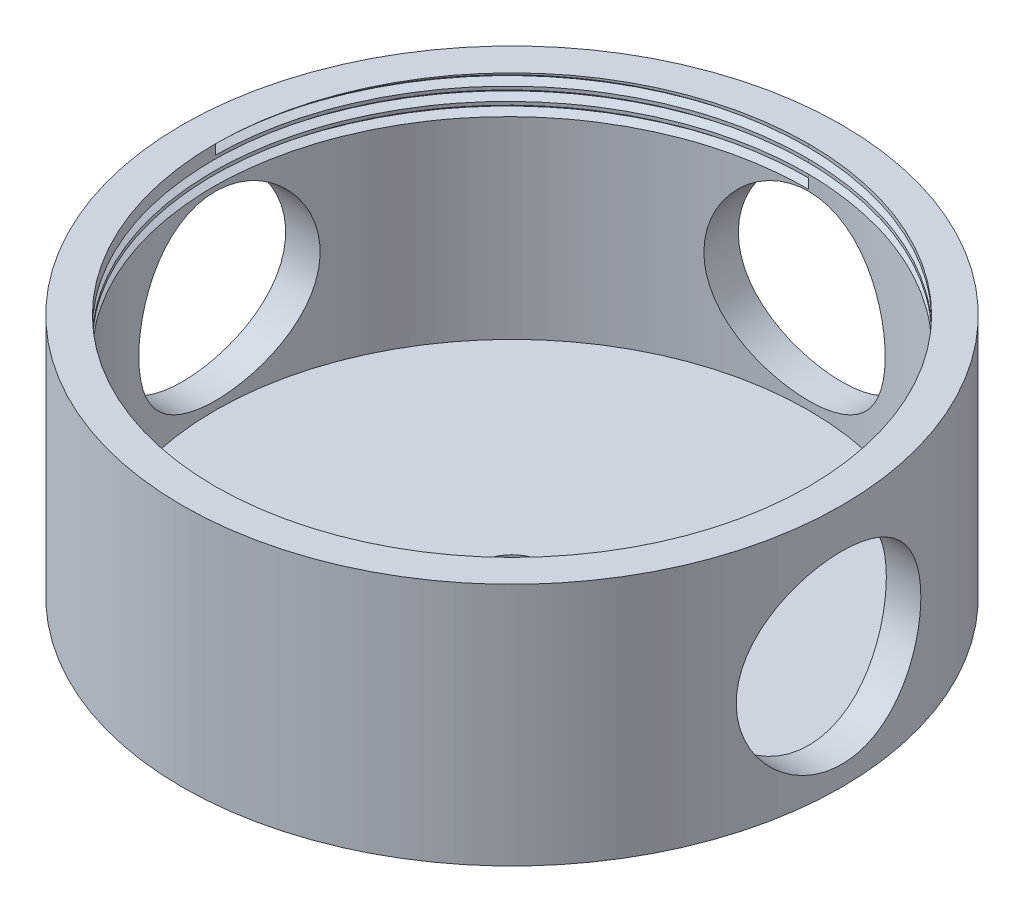
SolidWorks part; units mm, degrees
ref_plane "Front Plane" through (0, 0, 0) normal (0, 0, 1) x (1, 0, 0)
ref_plane "Top Plane" through (0, 0, 0) normal (0, 1, 0) x (1, 0, 0)
ref_plane "Right Plane" through (0, 0, 0) normal (1, 0, 0) x (0, 0, -1)
sketch "Sketch1" plane through (0, 0, 0) normal (0, 1, 0) x (1, 0, 0)
  circle A0 centre (0, 0) radius 50
  dimension "D1" = 100
extrude "Boss-Extrude1" add sketch "Sketch1" along normal blind 2 contours A0
sketch "Sketch2" plane through (0, 2, 0) normal (0, 1, 0) x (1, 0, 0)
  circle A0 centre (0, 0) radius 50
  circle A1 centre (0, 0) radius 45
  dimension "D1" = 100
  dimension "D2" = 5
extrude "Boss-Extrude2" add sketch "Sketch2" along normal blind 35
ref_plane "Plane3" through (0, 0, 40) normal (0, 0, 1) x (1, 0, 0)
sketch "Sketch5" plane through (0, 0, 40) normal (0, 0, 1) x (1, 0, 0)
  line L0 (-50, 0) -> (50, 0) construction
  line L1 (-26.6422, 0) -> (27.3578, 0)
  line L2 (-26.6422, 0) -> (-26.6422, -34)
  line L3 (-26.6422, -34) -> (27.3578, -34)
  line L4 (27.3578, 0) -> (27.3578, -34)
  line L5 (-50, 0) -> (50, 0) construction
  line L6 (-24.6422, -2) -> (25.3578, -2)
  line L7 (-24.6422, -2) -> (-24.6422, -32)
  line L8 (-24.6422, -32) -> (25.3578, -32)
  line L9 (25.3578, -2) -> (25.3578, -32)
  dimension "D1" = 2
  dimension "D2" = 2
  dimension "D3" = 2
  dimension "D4" = 2
  dimension "D5" = 50
  dimension "D6" = 2
  dimension "D7" = 30
thread "Thread1" pitch 2 method cut profile "Thread Profile1" start angle 0, offset 0, length 4.5, pitch 2, diameter 90
ref_plane "Plane4" through (-45, 37, 0) normal (0, 0, 1) x (-1, 0, 0)
sketch "Thread Profile1" plane through (-45, 37, 0) normal (0, 0, 1) x (-1, 0, 0)
  line L0 (0, 0) -> (0, 2) construction
  line L1 (0, 0) -> (1.0825, 0.625)
  line L2 (1.0825, 0.625) -> (1.0825, 0.875)
  line L3 (1.0825, 0.875) -> (0, 1.5)
  line L4 (1.0825, 0.75) -> (0, 0.75) construction
  line L11 (0, 0) -> (0, 1.5)
  point P2 (0, 0)
  dimension "Pitch" = 2
  dimension "Profile_Angle" = 60
  dimension "Profile_Land" = 0.25
  dimension "Profile_Height" = 1.0825
ref_plane "Plane6" through (0, 0, -50) normal (0, 0, -1) x (-1, 0, 0)
sketch "Sketch10" plane through (0, 0, -50) normal (0, 0, -1) x (-1, 0, 0)
  line L0 (0, 17) -> (-42.3594, 17) construction
  line L1 (0, 37) -> (0, 0) construction
  line L2 (50, 37) -> (-50, 37) construction
  line L3 (-42.3594, 17) -> (37.1989, 17) construction
  circle A1 centre (0, 17) radius 13.75
  dimension "D2" = 27.5
  dimension "D5" = 37
  dimension "D6" = 20
extrude "Cut-Extrude2" cut sketch "Sketch10" against normal up to next
ref_plane "Plane8" through (-50, 0, 0) normal (-1, 0, 0) x (0, 0, 1)
sketch "Sketch12" plane through (-50, 0, 0) normal (-1, 0, 0) x (0, 0, 1)
  line L1 (50, 37) -> (-50, 37) construction
  circle A0 centre (0, 17) radius 13.75
  dimension "D1" = 27.5
  dimension "D2" = 20
extrude "Cut-Extrude4" cut sketch "Sketch12" against normal up to next
ref_plane "Plane9" through (50, 0, 0) normal (1, 0, 0) x (0, 0, -1)
sketch "Sketch13" plane through (50, 0, 0) normal (1, 0, 0) x (0, 0, -1)
  line L0 (50, 37) -> (-50, 37) construction
  circle A0 centre (0, 17) radius 14
  dimension "D1" = 28
  dimension "D2" = 20
extrude "Cut-Extrude5" cut sketch "Sketch13" against normal up to next
sketch "Sketch14" plane through (0, 2, 0) normal (0, 1, 0) x (1, 0, 0)
  circle A0 centre (0, 0) radius 5
  dimension "D1" = 10
extrude "Cut-Extrude6" cut sketch "Sketch14" against normal up to next
